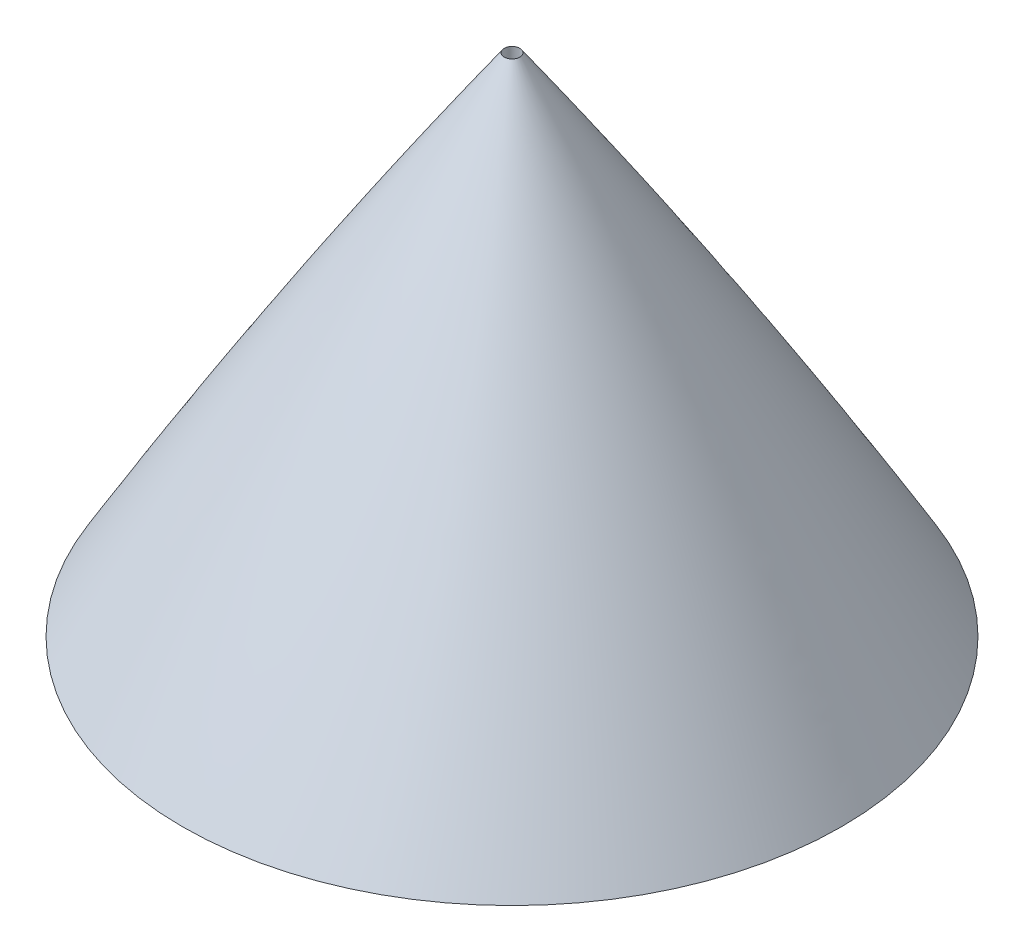
SolidWorks part; units mm, degrees
material "1060 Alloy"
ref_plane "Front Plane" through (0, 0, 0) normal (0, 0, 1) x (1, 0, 0)
ref_plane "Top Plane" through (0, 0, 0) normal (0, 1, 0) x (1, 0, 0)
ref_plane "Right Plane" through (0, 0, 0) normal (1, 0, 0) x (0, 0, -1)
sketch "Sketch1" plane through (0, 0, 0) normal (0, 0, 1) x (1, 0, 0)
  line L0 (81.2, 1.3793) -> (81.2, 151.3793)
  line L2 (71.2, 1.3793) -> (71.2, 151.2679)
  line L3 (0, 0) -> (0.8486, 381.4033)
  line L4 (71.2, 1.3793) -> (81.2, 1.3793)
  line L5 (0.4588, 400) -> (0.8486, 381.4033)
  line L6 (0, -198.8179) -> (0, -350.074)
  spline S0 degree 4 poles (-15.1078, 421.1353) (-14.7669, 420.6993) (-14.0862, 419.8261) (-13.069, 418.5123) (-11.7228, 416.7561) (-10.3886, 414.9975) (-9.0739, 413.2477) (-7.764, 411.4856) (-6.4874, 409.7528) (-5.1817, 407.9597) (-3.9585, 406.2673) (-2.5969, 404.357) (-1.5373, 402.8642) (0.0254, 400.6264) (0.7367, 399.6007) (2.0205, 397.7345) (3.0199, 396.2669) (4.0187, 394.7875) (5.0298, 393.2778) (6.0272, 391.7752) (7.0201, 390.2665) (8.0124, 388.7456) (9.0039, 387.2124) (17.2164, 374.4011) (29.2889, 353.6408) (43.7879, 324.1978) (59.1976, 283.601) (70.5335, 243.5908) (76.5329, 210.8551) (79.3409, 185.6146) (80.3563, 170.8833) (80.5516, 167.669) (80.6998, 164.9243) (80.7904, 163.1105) (80.8734, 161.3064) (80.9492, 159.5045) (81.018, 157.6887) (81.079, 155.9051) (81.1326, 154.1294) (81.1903, 151.8635) (81.2174, 150.6129) (81.2679, 147.8728) (81.2875, 146.0369) (81.3081, 143.6793) (81.3124, 141.5836) (81.3092, 139.3554) (81.2939, 137.1946) (81.2689, 134.9895) (81.2326, 132.7922) (81.1856, 130.5758) (81.1274, 128.3545) (81.0757, 126.6867) (81.0375, 125.5756) (81.0176, 125.0201) knots 0 0 0 0 0 0.006969 0.013937 0.020906 0.027875 0.034717 0.04156 0.048403 0.055246 0.062088 0.068931 0.075774 0.082616 0.0883 0.093983 0.099666 0.10535 0.111033 0.116716 0.122399 0.128083 0.133891 0.1397 0.313954 0.430124 0.546294 0.685698 0.836718 0.848335 0.865761 0.871569 0.877253 0.882936 0.888619 0.894302 0.899986 0.905669 0.911352 0.917035 0.923907 0.930779 0.93765 0.944522 0.951393 0.958265 0.965136 0.972008 0.979006 0.986004 0.993002 1 1 1 1 1 construction
  spline S1 degree 4 poles (0.4588, 400) (0.6734, 399.6903) (1.1044, 399.0662) (2.0205, 397.7345) (3.0199, 396.2669) (4.0187, 394.7875) (5.0298, 393.2778) (6.0272, 391.7752) (7.0201, 390.2665) (8.0124, 388.7456) (9.0039, 387.2124) (17.2164, 374.4011) (29.2889, 353.6408) (43.7879, 324.1978) (59.1976, 283.601) (70.5335, 243.5908) (76.5329, 210.8551) (79.3409, 185.6146) (80.3563, 170.8833) (80.5516, 167.669) (80.6998, 164.9243) (80.7904, 163.1105) (80.8734, 161.3064) (80.9492, 159.5045) (81.018, 157.6887) (81.079, 155.9051) (81.1326, 154.1294) (81.1737, 152.5144) (81.1917, 151.7559) (81.2, 151.3793) knots 0.082616 0.082616 0.082616 0.082616 0.082616 0.0883 0.093983 0.099666 0.10535 0.111033 0.116716 0.122399 0.128083 0.133891 0.1397 0.313954 0.430124 0.546294 0.685698 0.836718 0.848335 0.865761 0.871569 0.877253 0.882936 0.888619 0.894302 0.899986 0.905669 0.911352 0.917035 0.917035 0.917035 0.917035 0.917035
  spline S2 degree 1 poles (-7.7609, 394.3048) (71.2, 151.2679) knots 0 0 1 1 construction
  spline S3 degree 3 poles (-7.7609, 394.3048) (-7.5922, 394.0613) (-7.2817, 393.6117) (-6.6601, 392.7086) (-6.032, 391.7919) (-5.4585, 390.9501) (-4.8996, 390.1251) (-4.15, 389.0135) (-2.8297, 387.0417) (-0.9749, 384.2298) (3.4251, 377.4255) (12.6153, 362.4762) (30.6345, 329.2189) (51.0726, 279.086) (64.0054, 226.5145) (68.9758, 189.0173) (70.3277, 171.5214) (70.7675, 163.4302) (70.9198, 160.0654) (71.0106, 157.6941) (71.0576, 156.3527) (71.0904, 155.3556) (71.121, 154.3456) (71.1515, 153.2436) (71.1749, 152.3255) (71.1903, 151.692) (71.1968, 151.4123) (71.2, 151.2679) knots 0.082616 0.082616 0.082616 0.082616 0.085874 0.089132 0.09239 0.095648 0.098905 0.102163 0.108679 0.12171 0.134741 0.186866 0.291115 0.499613 0.708111 0.81236 0.864485 0.877516 0.890547 0.897063 0.90032 0.903578 0.906836 0.910094 0.913352 0.914981 0.916609 0.916609 0.916609 0.916609 only from (0.8486, 381.4033) to (71.2, 151.2679)
  point P11 (0.4588, 400)
  dimension "D1" = 400
  dimension "D2" = 150
  dimension "D3" = 81.2
  dimension "D4" = 10
revolve "Revolve3" add sketch "Sketch1" angle 360 about L6 reverse direction yes
ref_plane "Plane1" through (0, 151.3793, 0) normal (0, 1, 0) x (1, 0, 0)
sketch "Sketch2" plane through (0, 151.3793, 0) normal (0, 1, 0) x (1, 0, 0)
  circle A0 centre (0, 0) radius 71.2 construction
  circle A1 centre (0, 0) radius 71.2
  circle A2 centre (0, 0) radius 63.2
  dimension "D1" = 8
extrude "Boss-Extrude1" add sketch "Sketch2" against normal blind 300
ref_plane "Plane2" through (0, 400, 0) normal (0, -1, 0) x (-1, 0, 0)
ref_plane "Plane4" through (0, 370, 0) normal (0, -1, 0) x (-1, 0, 0)
sketch "Sketch3" plane through (0, 370, 0) normal (0, -1, 0) x (-1, 0, 0)
  circle A0 centre (0, 0) radius 120.7266
extrude "Cut-Extrude1" cut sketch "Sketch3" along normal through all
